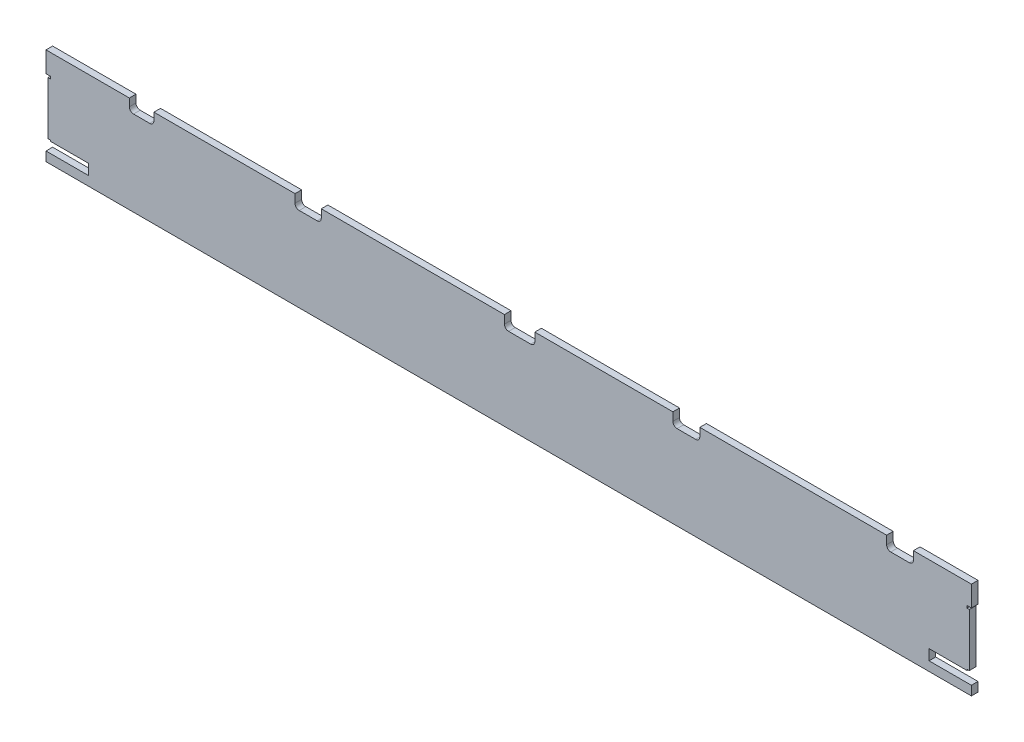
SolidWorks part; units mm, degrees
material "PP Film"
ref_plane "X-Y Datum" through (0, 0, 0) normal (0, 0, 1) x (1, 0, 0)
ref_plane "X-Z Datum" through (0, 0, 0) normal (0, 1, 0) x (1, 0, 0)
ref_plane "Y-Z Datum" through (0, 0, 0) normal (1, 0, 0) x (0, 0, -1)
sketch "Sketch2" plane through (0, 0, 0) normal (0, 0, 1) x (1, 0, 0)
  line L0 (-174.4992, -157.216) -> (269.7668, -157.216)
  line L20 (-154.1792, -199.261) -> (-174.4992, -199.261)
  line L21 (249.4468, -194.181) -> (267.6238, -194.181)
  line L22 (267.6238, -194.181) -> (267.6238, -193.665)
  line L23 (267.6238, -193.665) -> (268.7668, -193.665)
  line L24 (268.7668, -193.665) -> (268.7668, -168.265)
  line L25 (268.7668, -168.265) -> (267.6238, -168.265)
  line L26 (267.6238, -168.265) -> (267.6238, -167.122)
  line L27 (267.6238, -167.122) -> (269.7668, -167.122)
  line L28 (269.7668, -167.122) -> (269.7668, -157.216)
  line L29 (269.7668, -157.216) -> (241.9429, -157.216)
  line L30 (-174.4992, -157.216) -> (-174.4992, -167.122)
  line L31 (-174.4992, -167.122) -> (-172.3562, -167.122)
  line L32 (-172.3562, -167.122) -> (-172.3562, -168.265)
  line L33 (-172.3562, -168.265) -> (-173.4992, -168.265)
  line L34 (-173.4992, -168.265) -> (-173.4992, -193.665)
  line L35 (-173.4992, -193.665) -> (-172.3562, -193.665)
  line L36 (-172.3562, -193.665) -> (-172.3562, -194.181)
  line L37 (-172.3562, -194.181) -> (-154.1792, -194.181)
  line L38 (-154.1792, -194.181) -> (-154.1792, -199.261)
  line L39 (-154.1792, -203.714) -> (249.4468, -203.714)
  line L41 (249.4468, -194.181) -> (267.6238, -194.181)
  line L42 (267.6238, -194.181) -> (267.6238, -193.665)
  line L43 (267.6238, -193.665) -> (268.7668, -193.665)
  line L44 (268.7668, -193.665) -> (268.7668, -168.265)
  line L45 (268.7668, -168.265) -> (267.6238, -168.265)
  line L46 (267.6238, -168.265) -> (267.6238, -167.122)
  line L47 (267.6238, -167.122) -> (269.7668, -167.122)
  line L48 (269.7668, -167.122) -> (269.7668, -157.216)
  line L50 (-174.4992, -157.216) -> (-174.4992, -167.122)
  line L51 (-174.4992, -167.122) -> (-172.3562, -167.122)
  line L52 (-172.3562, -167.122) -> (-172.3562, -168.265)
  line L53 (-172.3562, -168.265) -> (-173.4992, -168.265)
  line L54 (-173.4992, -168.265) -> (-173.4992, -193.665)
  line L55 (-173.4992, -193.665) -> (-172.3562, -193.665)
  line L56 (-172.3562, -193.665) -> (-172.3562, -194.181)
  line L57 (-172.3562, -194.181) -> (-154.1792, -194.181)
  line L58 (-154.1792, -194.181) -> (-154.1792, -199.261)
  line L59 (-154.1792, -203.714) -> (249.4468, -203.714)
  line L124 (-154.1792, -199.261) -> (-174.4992, -199.261)
  line L196 (-174.4992, -199.261) -> (-174.4992, -203.714)
  line L197 (-174.4992, -199.261) -> (-174.4992, -203.714)
  line L198 (-174.4992, -203.714) -> (-154.1792, -203.714)
  line L199 (-174.4992, -203.714) -> (-154.1792, -203.714)
  line L200 (249.4468, -203.714) -> (269.7668, -203.714)
  line L201 (249.4468, -203.714) -> (269.7668, -203.714)
  line L202 (269.7668, -203.714) -> (269.7668, -199.261)
  line L203 (269.7668, -203.714) -> (269.7668, -199.261)
  line L204 (269.7668, -199.261) -> (249.4468, -199.261)
  line L205 (269.7668, -199.261) -> (249.4468, -199.261)
  line L206 (249.4468, -199.261) -> (249.4468, -194.181)
  line L207 (249.4468, -199.261) -> (249.4468, -194.181)
  line L611 (-134.4822, -157.216) -> (-174.4992, -157.216)
  line L612 (-122.6909, -162.8707) -> (-134.4822, -162.8707)
  line L613 (-122.6909, -162.8707) -> (-134.4822, -162.8707)
  line L614 (-134.4822, -162.8707) -> (-134.4822, -157.216)
  line L615 (-134.4822, -162.8707) -> (-134.4822, -157.216)
  line L616 (241.9429, -157.216) -> (241.9429, -163.2039)
  line L617 (241.9429, -157.216) -> (241.9429, -163.2039)
  line L618 (241.9429, -163.2039) -> (229.0538, -163.2039)
  line L619 (241.9429, -163.2039) -> (229.0538, -163.2039)
  line L620 (229.0538, -163.2039) -> (229.0538, -157.216)
  line L621 (229.0538, -163.2039) -> (229.0538, -157.216)
  line L622 (229.0538, -157.216) -> (139.3917, -157.216)
  line L623 (229.0538, -157.216) -> (139.3917, -157.216)
  line L624 (139.3917, -157.216) -> (139.3917, -163.2039)
  line L625 (139.3917, -157.216) -> (139.3917, -163.2039)
  line L626 (139.3917, -163.2039) -> (126.4593, -163.2039)
  line L627 (139.3917, -163.2039) -> (126.4593, -163.2039)
  line L628 (126.4593, -163.2039) -> (126.4593, -157.216)
  line L629 (126.4593, -163.2039) -> (126.4593, -157.216)
  line L630 (126.4593, -157.216) -> (60.1739, -157.216)
  line L631 (126.4593, -157.216) -> (60.1739, -157.216)
  line L632 (60.1739, -157.216) -> (60.1739, -163.2039)
  line L633 (60.1739, -157.216) -> (60.1739, -163.2039)
  line L634 (60.1739, -163.2039) -> (45.5847, -163.2039)
  line L635 (60.1739, -163.2039) -> (45.5847, -163.2039)
  line L636 (45.5847, -163.2039) -> (45.5847, -157.216)
  line L637 (45.5847, -163.2039) -> (45.5847, -157.216)
  line L638 (45.5847, -157.216) -> (-42.3503, -157.216)
  line L639 (45.5847, -157.216) -> (-42.3503, -157.216)
  line L640 (-42.3503, -157.216) -> (-42.3503, -163.2039)
  line L641 (-42.3503, -157.216) -> (-42.3503, -163.2039)
  line L642 (-42.3503, -163.2039) -> (-54.941, -163.2039)
  line L643 (-42.3503, -163.2039) -> (-54.941, -163.2039)
  line L644 (-54.941, -163.2039) -> (-54.941, -157.216)
  line L645 (-54.941, -163.2039) -> (-54.941, -157.216)
  line L646 (-54.941, -157.216) -> (-122.6909, -157.216)
  line L647 (-54.941, -157.216) -> (-122.6909, -157.216)
  line L648 (-122.6909, -157.216) -> (-122.6909, -162.8707)
  line L649 (-122.6909, -157.216) -> (-122.6909, -162.8707)
  dimension "D1" = 0
extrude "Boss-Extrude1" add sketch "Sketch2" along normal blind 3.175 contours L58 L59 L41 L42 L43 L44 L45 L46 L47 L48 L50 L51 L52 L53 L54 L55 L56 L57 region at (47.5062, -180.687, 0)
sketch "Sketch3" [suppressed] plane through (0, 0, 3.175) normal (0, 0, 1) x (1, 0, 0)
  line L0 (-174.4992, -157.216) -> (-134.4822, -157.216) construction
  line L2 (-134.4822, -157.216) -> (-134.4822, -162.8707)
  line L3 (-134.4822, -162.8707) -> (-122.6909, -162.8707)
  line L4 (-122.6909, -157.216) -> (-122.6909, -162.8707)
  line L5 (-54.941, -157.216) -> (-42.3503, -157.216)
  line L6 (-54.941, -157.216) -> (-54.941, -163.2039)
  line L7 (-54.941, -163.2039) -> (-42.3503, -163.2039)
  line L8 (-42.3503, -157.216) -> (-42.3503, -163.2039)
  line L9 (237.3358, -161.2338) -> (242.4154, -163.4059) construction
  line L10 (45.5847, -157.216) -> (60.1739, -157.216)
  line L11 (45.5847, -157.216) -> (45.5847, -163.2039)
  line L12 (45.5847, -163.2039) -> (60.1739, -163.2039)
  line L13 (60.1739, -157.216) -> (60.1739, -163.2039)
  line L14 (126.4593, -157.216) -> (139.3917, -157.216)
  line L15 (126.4593, -157.216) -> (126.4593, -163.2039)
  line L16 (126.4593, -163.2039) -> (139.3917, -163.2039)
  line L17 (139.3917, -157.216) -> (139.3917, -163.2039)
  line L18 (229.0538, -157.216) -> (241.9429, -157.216)
  line L19 (229.0538, -157.216) -> (229.0538, -163.2039)
  line L20 (229.0538, -163.2039) -> (241.9429, -163.2039)
  line L21 (241.9429, -157.216) -> (241.9429, -163.2039)
  line L22 (-134.4822, -157.216) -> (-122.6909, -157.216)
extrude "Cut-Extrude1" [suppressed] cut sketch "Sketch3" against normal through all both and the other way through all
fillet "Fillet1" radius 2 10 edges at (241.9429, -163.2039, 1.5875) (229.0538, -163.2039, 1.5875) (126.4593, -163.2039, 1.5875) (139.3917, -163.2039, 1.5875) (60.1739, -163.2039, 1.5875) (45.5847, -163.2039, 1.5875) (-54.941, -163.2039, 1.5875) (-42.3503, -163.2039, 1.5875) (-122.6909, -162.8707, 1.5875) (-134.4822, -162.8707, 1.5875)
